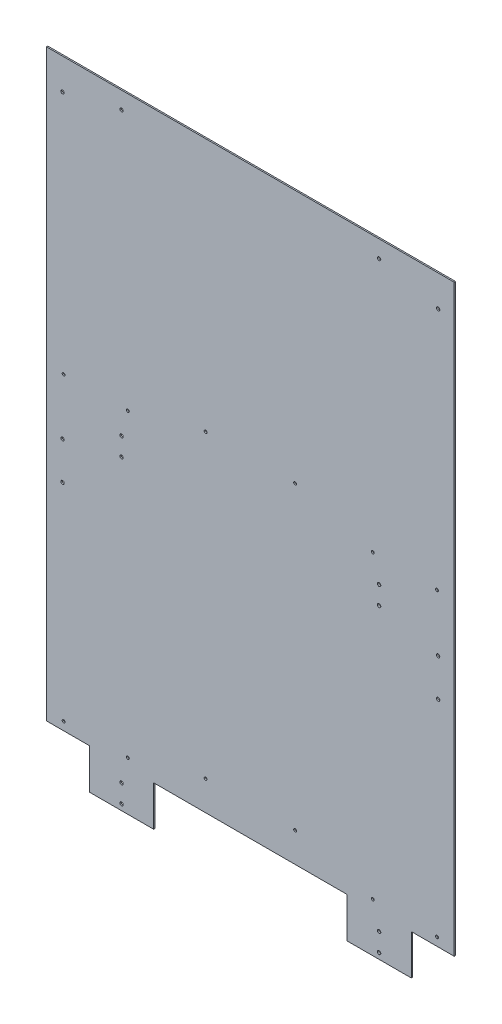
SolidWorks part; units mm, degrees
material "PC High Viscosity"
ref_plane "Front Plane" through (0, 0, 0) normal (0, 0, 1) x (1, 0, 0)
ref_plane "Top Plane" through (0, 0, 0) normal (0, 1, 0) x (1, 0, 0)
ref_plane "Right Plane" through (0, 0, 0) normal (1, 0, 0) x (0, 0, -1)
sketch "Sketch2" plane through (0, 0, 0) normal (0, 0, 1) x (1, 0, 0)
  line L0 (-482.6, 0) -> (-381, 0)
  line L2 (-482.6, 0) -> (-482.6, 1409.7)
  line L3 (-482.6, 1409.7) -> (482.6, 1409.7)
  line L4 (482.6, 0) -> (482.6, 1409.7)
  line L5 (-381, 0) -> (-381, -95.25)
  line L6 (-381, -95.25) -> (-228.6, -95.25)
  line L7 (-228.6, -95.25) -> (-228.6, 0)
  line L8 (-228.6, 0) -> (228.6, 0)
  line L9 (228.6, 0) -> (228.6, -95.25)
  line L10 (228.6, -95.25) -> (381, -95.25)
  line L11 (381, -95.25) -> (381, 0)
  line L12 (381, 0) -> (482.6, 0)
  line L13 (0, 0) -> (0, 1409.7) construction
  dimension "D2" = 965.2
  dimension "D1" = 1409.7
  dimension "D3" = 95.25
  dimension "D5" = 152.4
  dimension "D4" = 457.2
extrude "Boss-Extrude1" add sketch "Sketch2" along normal blind 3.175
hole_wizard "1/4 Clearance Hole1" positions "Sketch3" profile "Sketch4" hole size "1/4" standard "ANSI Inch" end condition through all
sketch "Sketch3" plane through (0, 0, 3.175) normal (0, 0, 1) x (1, 0, 0)
  line L0 (0, 0) -> (0, 1409.7) construction
  line L4 (-9.861, 81.3082) -> (0, 118.11) construction
  line L5 (-9.861, 81.3082) -> (472.739, -48.0041) construction
  line L6 (0, 118.11) -> (482.6, -11.2023) construction
  line L7 (472.739, -48.0041) -> (482.6, -11.2023) construction
  line L8 (482.6, 0) -> (482.6, 1409.7) construction
  line L9 (12.7, 114.707) -> (2.839, 77.9053) construction
  line L11 (-4.9305, 99.7091) -> (477.6695, -29.6032) construction
  line L13 (289.9164, 20.7051) -> (289.9164, 731.9051) construction
  line L14 (0, 118.11) -> (1.6435, 124.2436) construction
  line L15 (0, 118.11) -> (480.9565, -10.7619) construction
  line L16 (1.6435, 124.2436) -> (482.6, -4.6283) construction
  line L17 (480.9565, -10.7619) -> (482.6, -4.6283) construction
  line L18 (482.6, 1409.7) -> (-482.6, 1409.7) construction
  line L20 (-228.6, 0) -> (228.6, 0) construction
  line L21 (-381, -95.25) -> (-228.6, -95.25) construction
  circle A0 centre (441.96, 19.4092) radius 6.35 construction
  point P178 (105.9076, 70.0101)
  point P180 (289.9164, 20.7051)
  point P183 (-289.9164, 20.7051)
  point P184 (-105.9076, 70.0101)
  point P195 (105.9076, 781.2101)
  point P196 (289.9164, 731.9051)
  point P197 (-289.9164, 731.9051)
  point P198 (-105.9076, 781.2101)
  point P566 (441.96, 19.4092)
  point P569 (-441.96, 19.4092)
  point P573 (-441.96, 730.6092)
  point P576 (441.96, 730.6092)
  dimension "D10" = 12.7
  dimension "D11" = 6.35
  dimension "D2" = 12.7
  dimension "D3" = 38.1
  dimension "D4" = 213.36
  dimension "D5" = 101.6
  dimension "D6" = 292.1
  dimension "D8" = 711.2
  dimension "D9" = 6.35
  dimension "D12" = 439.2982
  dimension "D13" = 15
  dimension "D14" = 441.96
  dimension "D7" = 2
sketch "Sketch4" plane through (441.96, 730.6092, 3.175) normal (1, 0, 0) x (0, -1, 0)
  line L0 (0, 0) -> (0, 3.175)
  line L1 (0, 3.175) -> (3.3782, 3.175)
  line L2 (3.3782, 3.175) -> (3.3782, 0)
  line L5 (3.3782, 0) -> (0, 0)
  line L11 (0, -6.35) -> (0, 107.95) construction
  dimension "Thru Hole Dia." = 6.7564
  dimension "Thru Hole Depth" = 3.175
hole_wizard "5/16 (0.3125) Diameter Hole1" positions "Sketch5" profile "Sketch6" hole size "5/16" standard "ANSI Inch" end condition through all
sketch "Sketch5" plane through (0, 0, 3.175) normal (0, 0, 1) x (1, 0, 0)
  line L0 (0, 1409.7) -> (0, -95.25) construction
  line L1 (482.6, 1409.7) -> (-482.6, 1409.7) construction
  line L3 (-482.6, 1381.76) -> (482.6, 1381.76) construction
  line L4 (-482.6, 1381.76) -> (-482.6, 1343.66) construction
  line L5 (-482.6, 1343.66) -> (482.6, 1343.66) construction
  line L6 (482.6, 1381.76) -> (482.6, 1343.66) construction
  line L7 (-482.6, 1409.7) -> (-482.6, 0) construction
  line L8 (482.6, 0) -> (482.6, 1409.7) construction
  line L9 (-304.8, -95.25) -> (-304.8, 1409.7) construction
  line L10 (-381, -95.25) -> (-228.6, -95.25) construction
  point P13 (-304.8, 1341.12)
  point P17 (304.8, 1341.12)
  point P181 (-304.8, 673.1)
  point P182 (-304.8, 629.92)
  point P183 (304.8, 673.1)
  point P184 (304.8, 629.92)
  point P185 (-304.8, -38.1)
  point P186 (-304.8, -81.28)
  point P187 (304.8, -38.1)
  point P188 (304.8, -81.28)
  point P189 (-444.5, 1308.1)
  point P191 (444.5, 1308.1)
  point P200 (-444.5, 596.9)
  point P201 (444.5, 596.9)
  point P211 (-444.5, 508)
  point P213 (444.5, 508)
  dimension "D1" = 38.1
  dimension "D2" = 27.94
  dimension "D3" = 43.18
  dimension "D4" = 2.54
  dimension "D6" = 711.2
  dimension "D7" = 444.5
  dimension "D8" = 101.6
  dimension "D10" = 711.2
  dimension "D11" = 43.18
  dimension "D12" = 88.9
  dimension "D5" = 3
  dimension "D9" = 2
sketch "Sketch6" plane through (444.5, 508, 3.175) normal (1, 0, 0) x (0, -1, 0)
  line L0 (0, 0) -> (0, 3.175)
  line L1 (0, 3.175) -> (3.9687, 3.175)
  line L2 (3.9687, 3.175) -> (3.9687, 0)
  line L5 (3.9687, 0) -> (0, 0)
  line L11 (0, -6.35) -> (0, 107.95) construction
  dimension "Thru Hole Dia." = 7.9375
  dimension "Thru Hole Depth" = 3.175
sketch "Sketch7" plane through (0, 0, 3.175) normal (0, 0, 1) x (1, 0, 0)
  line L0 (482.6, 0) -> (482.6, 1409.7) construction
  line L1 (-482.6, 1409.7) -> (482.6, 1409.7)
  line L2 (-482.6, 1409.7) -> (-482.6, 1381.76)
  line L3 (-482.6, 1381.76) -> (482.6, 1381.76)
  line L4 (482.6, 1409.7) -> (482.6, 1381.76)
  dimension "D1" = 27.94
extrude "Cut-Extrude1" cut sketch "Sketch7" against normal through all
equation "\"D3@Sketch2\"=59.25-\"D1@Sketch2\""
